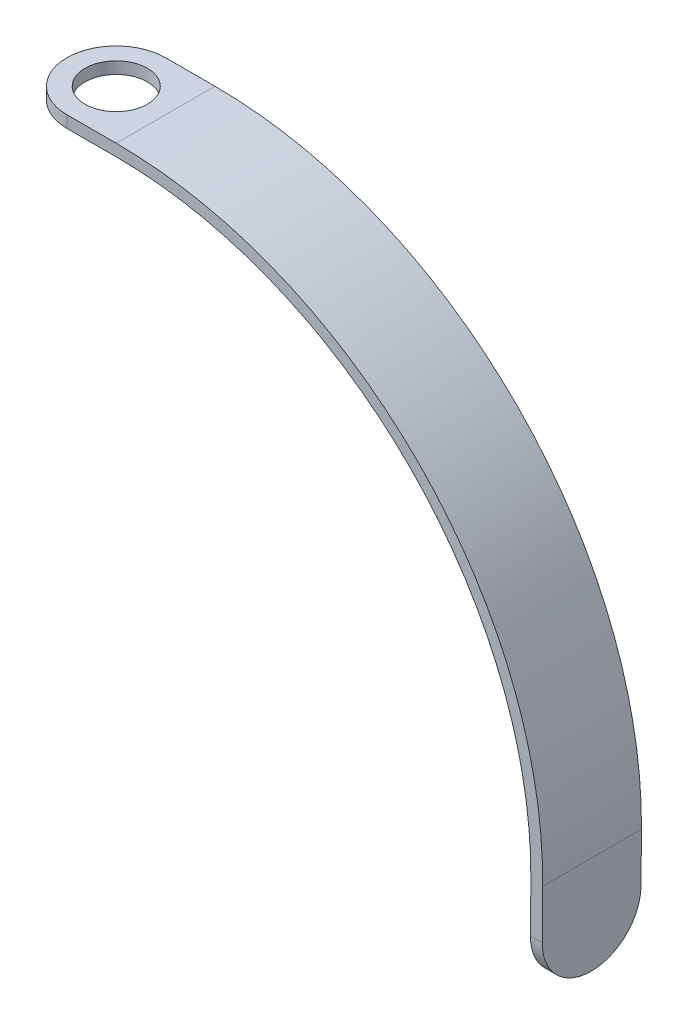
SolidWorks part; units mm, degrees
ref_plane "Front Plane" through (0, 0, 0) normal (0, 0, 1) x (1, 0, 0)
ref_plane "Top Plane" through (0, 0, 0) normal (0, 1, 0) x (1, 0, 0)
ref_plane "Right Plane" through (0, 0, 0) normal (1, 0, 0) x (0, 0, -1)
sketch "Sketch2" plane through (0, 0, 0) normal (0, 0, 1) x (1, 0, 0)
  line L0 (0, 0) -> (0, 105) construction
  line L1 (0, 0) -> (104.996, -0.9163) construction
  line L4 (0, 108) -> (-25, 108)
  line L5 (-25, 108) -> (-25, 105)
  line L6 (-25, 105) -> (0, 105)
  line L7 (104.996, -0.9163) -> (104.7778, -25.9153)
  line L8 (104.7778, -25.9153) -> (107.7777, -25.9415)
  line L9 (107.7777, -25.9415) -> (107.9959, -0.9425)
  arc A0 (0, 105) -> (104.996, -0.9163) centre (0, 0) cw
  arc A1 (0, 108) -> (107.9959, -0.9425) centre (0, 0) cw
  dimension "D2" = 105
  dimension "D1" = 90.5
  dimension "D3" = 3
  dimension "D4" = 25
  dimension "D5" = 25
extrude "Boss-Extrude1" add sketch "Sketch2" along normal blind 25
fillet "Fillet1" radius 12.5 4 edges at (106.2778, -25.9284, 0) (106.2778, -25.9284, 25) (-25, 106.5, 25) (-25, 106.5, 0)
sketch "Sketch3" plane through (0, 108, 0) normal (0, 1, 0) x (1, 0, 0)
  circle A0 centre (-12.5, -12.5) radius 7.89
  dimension "D1" = 15.78
sketch "Sketch4" plane through (104.996, -0.9163, 0) normal (1, -0.0087, 0) x (0, 0, -1)
  circle A0 centre (-12.5, -12.5) radius 3.225
  dimension "D1" = 6.45
extrude "Cut-Extrude1" cut sketch "Sketch3" against normal up to next
extrude "Boss-Extrude2" add sketch "Sketch4" against normal blind 6
equation "\"D1@Sketch2\"=362/4"
